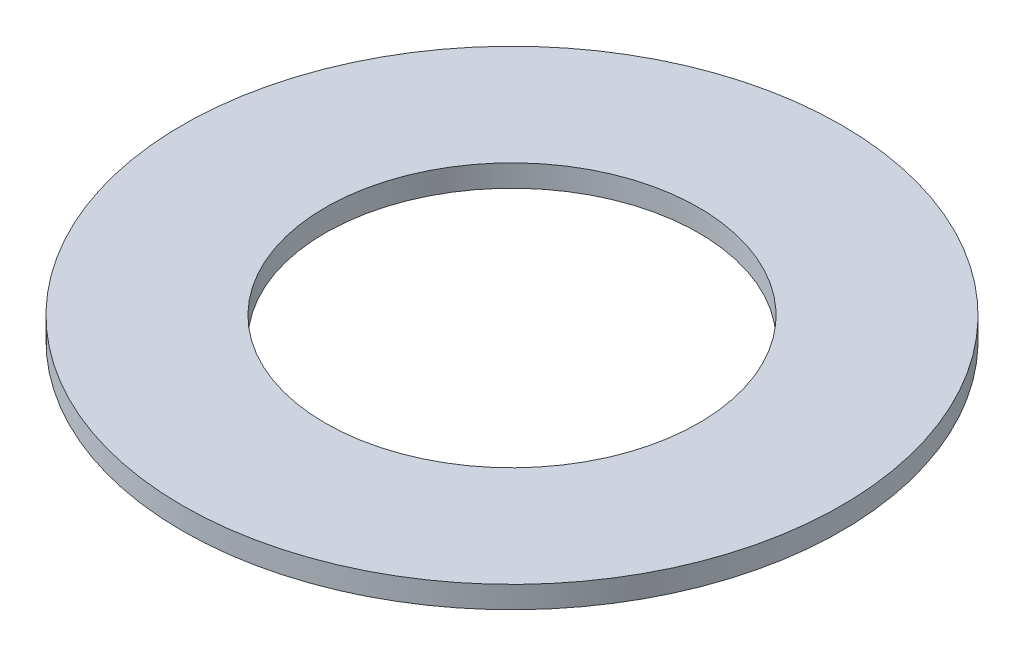
SolidWorks part; units mm, degrees
ref_plane "Front Plane" through (0, 0, 0) normal (0, 0, 1) x (1, 0, 0)
ref_plane "Top Plane" through (0, 0, 0) normal (0, 1, 0) x (1, 0, 0)
ref_plane "Right Plane" through (0, 0, 0) normal (1, 0, 0) x (0, 0, -1)
sketch "Sketch1" plane through (0, 0, 0) normal (0, 1, 0) x (1, 0, 0)
  circle A0 centre (0, 0) radius 75
  dimension "FLANGE_OD" = 150
extrude "Boss-Extrude1" add sketch "Sketch1" along normal blind 5
sketch "Sketch2" plane through (0, 0, 0) normal (0, 1, 0) x (1, 0, 0)
  circle A0 centre (0, 0) radius 42.5
  dimension "BORE_D" = 85
extrude "Cut-Extrude1" cut sketch "Sketch2" along normal through all
sketch "Sketch3" plane through (0, 5, 0) normal (0, 1, 0) x (1, 0, 0)
  circle A0 centre (0, 0) radius 29.3381 construction
  circle A1 centre (-29.3381, 0) radius 4.6149
  dimension "BOLT_D" = 9.2298
  dimension "BOLT_PCD" = 58.6761
extrude "Cut-Extrude2" cut sketch "Sketch3" against normal blind 4.1718 rebuild error yes
pattern_circular "CirPattern1" count 6 over 360 rebuild error yes
